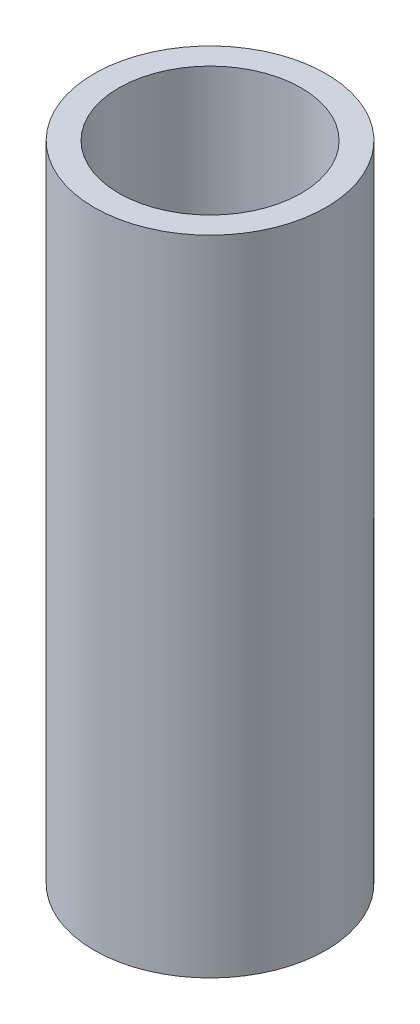
SolidWorks part; units mm, degrees
ref_plane "Front Plane" through (0, 0, 0) normal (0, 0, 1) x (1, 0, 0)
ref_plane "Top Plane" through (0, 0, 0) normal (0, 1, 0) x (1, 0, 0)
ref_plane "Right Plane" through (0, 0, 0) normal (1, 0, 0) x (0, 0, -1)
sketch "Sketch1" plane through (0, 0, 0) normal (0, 1, 0) x (1, 0, 0)
  circle A0 centre (0, 0) radius 5.08
  dimension "D1" = 10.16
extrude "Boss-Extrude1" add sketch "Sketch1" along normal blind 28.194
sketch "Sketch2" plane through (0, 28.194, 0) normal (0, 1, 0) x (1, 0, 0)
  circle A0 centre (0, 0) radius 4
  dimension "D1" = 8
sketch "Sketch3" plane through (0, 28.194, 0) normal (0, 1, 0) x (1, 0, 0)
  circle A0 centre (0, 0) radius 4
  dimension "D1" = 8
extrude "Cut-Extrude2" cut sketch "Sketch3" against normal through all
